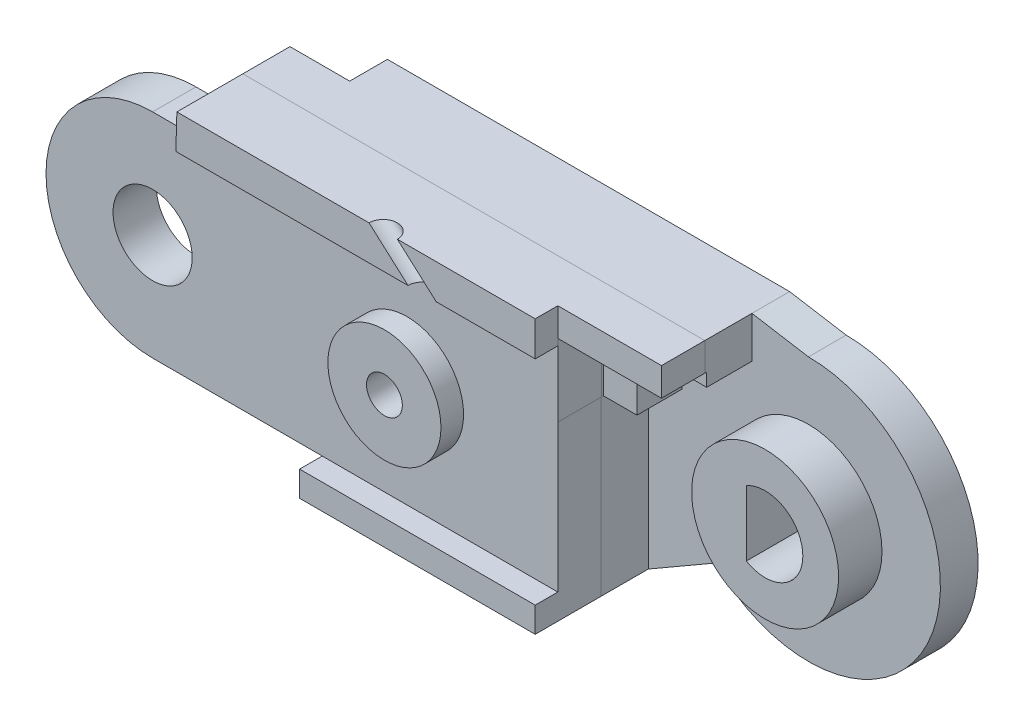
SolidWorks part; units mm, degrees
ref_plane "Front Plane" through (0, 0, 0) normal (0, 0, 1) x (1, 0, 0)
ref_plane "Top Plane" through (0, 0, 0) normal (0, 1, 0) x (1, 0, 0)
ref_plane "Right Plane" through (0, 0, 0) normal (1, 0, 0) x (0, 0, -1)
sketch "Sketch3" plane through (0, 0, 0) normal (0, 0, 1) x (1, 0, 0)
  line L7 (8, 0) -> (9, -2.5)
  line L11 (30, 7) -> (27, 7.5)
  line L13 (0, 7) -> (0, 7.5) construction
  line L14 (0, 7.5) -> (-22.3287, 7.5) construction
  line L15 (0, 5.3) -> (-14, 5.3) construction
  line L16 (0, 4) -> (-14, 4) construction
  line L17 (-14, 4) -> (-14, 5.3) construction
  line L18 (5.6569, 5.6569) -> (5.6569, 7.5)
  line L19 (5.6569, 7.5) -> (27, 7.5)
  line L20 (21.5, -7) -> (9, -7)
  line L21 (9, -7) -> (9, -2.5)
  line L23 (25.0503, -4.9497) -> (21.5, -7)
  arc A4 (8, 0) -> (5.6569, 5.6569) centre (0, 0) ccw
  arc A5 (25.0503, -4.9497) -> (30, 7) centre (30, 0) ccw
  circle A6 centre (0, 0) radius 7 construction
  circle A7 centre (0, 0) radius 3.9 construction
  circle A8 centre (0, 0) radius 5.3 construction
  circle A9 centre (0, 0) radius 4 construction
  dimension "D10" = 0.5
  dimension "D17" = 14
  dimension "D5" = 135
  dimension "D6" = 12.5
  dimension "D7" = 4.5
  dimension "D8" = 1
  dimension "D9" = 45
  dimension "D11" = 1.8431
  dimension "D12" = 30
  dimension "D14" = 3
extrude "Boss-Extrude1" add sketch "Sketch3" along normal blind 2 contours A5 L11 L19 L18 A4 L7 L21 L20 L23
sketch "Sketch20" plane through (0, 0, 0) normal (0, 0, 1) x (1, 0, 0)
  line L0 (0, 7) -> (0, 7.5) construction
  line L1 (0, 7.5) -> (-19.4737, 7.5) construction
  line L2 (0, 5.3) -> (-14, 5.3) construction
  line L3 (0, 4) -> (-14, 4) construction
  line L4 (-14, 4) -> (-14, 5.3) construction
  line L5 (0, 5.3) -> (17.4849, 5.3) construction
  line L6 (17.4849, 5.3) -> (17.4849, 4) construction
  line L7 (17.4849, 4) -> (0, 4) construction
  line L8 (-2.5, 7.5) -> (-2.5, 2.868) construction
  circle A0 centre (0, 0) radius 7 construction
  circle A1 centre (0, 0) radius 3.9 construction
  circle A3 centre (0, 0) radius 5.3 construction
  circle A4 centre (0, 0) radius 4 construction
  circle A5 centre (0, 0) radius 2 construction
  dimension "D1" = 0
  dimension "D2" = 2.5
ref_plane "Plane1" through (0, 0, 2) normal (0, 0, 1) x (1, 0, 0)
sketch "Sketch4" plane through (0, 0, 2) normal (0, 0, 1) x (1, 0, 0)
  line L4 (5.6569, 5.6569) -> (5.6569, 7.5)
  line L5 (5.6569, 5.6569) -> (5.6569, 7.5) construction
  line L6 (5.6569, 7.5) -> (21.5, 7.5)
  line L10 (8, 0) -> (9, -2.5)
  line L11 (9, -2.5) -> (9, -7)
  line L12 (9, -7) -> (21.5, -7)
  line L13 (21.5, -7) -> (21.5, 7.5)
  arc A0 (8, 0) -> (5.6569, 5.6569) centre (0, 0) ccw construction
  arc A3 (8, 0) -> (5.6569, 5.6569) centre (0, 0) ccw
sketch "Sketch22" plane through (0, 0, 2) normal (0, 0, 1) x (1, 0, 0)
  line L0 (5.6569, 5.6569) -> (2.4868, 5.6569)
  line L1 (5.6569, 7.5) -> (21.5, 7.5)
  line L2 (5.6569, 7.5) -> (2.4868, 7.5)
  line L3 (2.4868, 7.5) -> (2.4868, 5.6569)
  line L4 (21.5, 2.172) -> (21.5, 0)
  line L6 (8, 0) -> (9, -2.5)
  line L7 (9, -2.5) -> (9, -7)
  line L8 (9, -7) -> (21.5, -7)
  line L9 (21.5, -7) -> (21.5, 0)
  line L10 (21.5, 7.5) -> (27, 7.5)
  line L11 (27, 7.5) -> (27, 2.172)
  line L12 (27, 2.172) -> (21.5, 2.172)
  arc A0 (8, 0) -> (5.6569, 5.6569) centre (0, 0) ccw
extrude "Boss-Extrude6" add sketch "Sketch22" along normal blind 2.5
sketch "Sketch25" plane through (0, 0, 2) normal (0, 0, 1) x (1, 0, 0)
  line L0 (0, 5.3) -> (18.0981, 5.3) construction
  line L1 (0, 4) -> (18.0981, 4) construction
  line L2 (18.0981, 4) -> (18.0981, 5.3) construction
sketch "Sketch26" plane through (0, 0, 2) normal (0, 0, 1) x (1, 0, 0)
  line L1 (18.0981, 5.3) -> (2.5301, 5.3)
  line L2 (18.0981, 4) -> (2.5301, 4)
  line L3 (2.5301, 5.3) -> (2.5301, 4)
  line L4 (18.0981, 5.3) -> (27, 5.3)
  line L5 (27, 2.172) -> (27, 7.5) construction
  line L6 (27, 5.3) -> (27, 4)
  line L7 (27, 4) -> (18.0981, 4)
extrude "Cut-Extrude6" cut sketch "Sketch26" along normal blind 2.4
sketch "Sketch31" plane through (0, 0, 4.5) normal (0, 0, 1) x (1, 0, 0)
  line L0 (2.4327, 5.6569) -> (0, 5.6569)
  line L4 (9, -5.6569) -> (0, -5.6569)
  line L5 (2.4327, 5.6569) -> (2.4868, 7.5)
  line L6 (2.4868, 7.5) -> (21.5, 7.5)
  line L7 (21.5, -7) -> (21.5, 2.172) construction
  line L8 (27, 7.5) -> (2.4868, 7.5) construction
  line L11 (21.5, -7) -> (9, -7)
  line L12 (9, -7) -> (9, -5.6569)
  line L13 (9, -2.5) -> (9, -7) construction
  line L14 (21.5, 2.172) -> (21.5, -7)
  line L15 (21.5, 7.5) -> (27, 7.5)
  line L16 (27, 7.5) -> (27, 2.172)
  line L17 (27, 2.172) -> (21.5, 2.172)
  arc A0 (0, 5.6569) -> (0, -5.6569) centre (0, 0) ccw
  dimension "D1" = 5.6569
extrude "Boss-Extrude14" add sketch "Sketch31" along normal blind 2.3 separate body
sketch "Sketch32" plane through (0, 0, 6.8) normal (0, 0, 1) x (1, 0, 0)
  circle A0 centre (0, 0) radius 2.1
extrude "Cut-Extrude7" cut sketch "Sketch32" against normal blind 2.3
sketch "Sketch33" plane through (0, 0, 6.8) normal (0, 0, 1) x (1, 0, 0)
  line L0 (2.4868, 7.5) -> (21.5, 7.5)
  line L1 (27, 7.5) -> (2.4868, 7.5) construction
  line L6 (9, -5.6569) -> (21.5, -5.6569)
  line L7 (21.5, -7) -> (21.5, 2.172) construction
  line L8 (21.5, -5.6569) -> (21.5, -7)
  line L9 (21.5, -7) -> (9, -7)
  line L10 (9, -7) -> (9, -5.6569)
  line L12 (2.4868, 7.5) -> (2.4327, 5.6569)
  line L13 (2.4327, 5.6569) -> (21.5, 5.6569)
  line L14 (21.5, 5.6569) -> (21.5, 7.5)
extrude "Boss-Extrude15" add sketch "Sketch33" along normal blind 1.2
sketch "Sketch34" plane through (0, 0, 2) normal (0, 0, 1) x (1, 0, 0)
  line L0 (30, 5.3) -> (18.0981, 5.3) construction
  line L1 (30, 4) -> (18.0981, 4) construction
  circle A0 centre (30, 0) radius 2 construction
  circle A1 centre (30, 0) radius 5.3 construction
  circle A2 centre (30, 0) radius 4 construction
sketch "Sketch35" plane through (0, 0, 6.8) normal (0, 0, 1) x (1, 0, 0)
  line L0 (27, 2.172) -> (27, 6)
  line L1 (27, 2.172) -> (21.5204, 2.172)
  line L2 (27, 6) -> (21.5204, 6)
  line L3 (21.5204, 2.172) -> (21.5204, 6)
  line L4 (27, 2.172) -> (27, 7.5) construction
  line L5 (27, 7.5) -> (21.5, 7.5) construction
  dimension "D1" = 1.5
extrude "Cut-Extrude8" cut sketch "Sketch35" against normal blind 2.4
sketch "Sketch36" plane through (0, 0, 4.4) normal (0, 0, 1) x (1, 0, 0)
  line L0 (27, 2.172) -> (27, 4)
  line L1 (27, 2.172) -> (23.3, 2.172)
  line L2 (27, 4) -> (23.3, 4)
  line L3 (23.3, 2.172) -> (23.3, 4)
  line L4 (21.5, -7) -> (21.5, 7.5) construction
  dimension "D1" = 1.8
extrude "Cut-Extrude9" cut sketch "Sketch36" against normal blind 2.4
sketch "Sketch37" plane through (0, 0, 2) normal (0, 0, 1) x (1, 0, 0)
  circle A0 centre (30, 0) radius 3.9
extrude "Boss-Extrude16" add sketch "Sketch37" along normal blind 2.3
sketch "Sketch39" plane through (0, 0, 4.3) normal (0, 0, 1) x (1, 0, 0)
  line L0 (29, 1.7321) -> (29, -1.7321)
  arc A0 (29, -1.7321) -> (29, 1.7321) centre (30, 0) ccw
  dimension "D2" = 4
  dimension "D1" = 1
extrude "Cut-Extrude10" cut sketch "Sketch39" against normal through all
sketch "Sketch43" plane through (0, 0, 6.8) normal (0, 0, 1) x (1, 0, 0)
  line L0 (21.5, -7) -> (21.5, 7.5) construction
  line L1 (21.5, -5.6569) -> (9, -5.6569) construction
  circle A0 centre (13.5, 0) radius 3
  dimension "D1" = 8
  dimension "D2" = 5.6569
extrude "Boss-Extrude17" add sketch "Sketch43" along normal blind 1.2
sketch "Sketch44" plane through (0, 0, 8) normal (0, 0, 1) x (1, 0, 0)
  circle A0 centre (13.5, 0) radius 0.95
extrude "Cut-Extrude11" cut sketch "Sketch44" against normal through all
sketch "Sketch45" plane through (0, 0, 0) normal (0, 0, -1) x (-1, 0, 0)
  circle A0 centre (-13.5, 0) radius 2
extrude "Cut-Extrude12" cut sketch "Sketch45" against normal blind 3.2
ref_plane "Plane17" through (0, 0, 8) normal (0, 0, 1) x (1, 0, 0)
sketch "Sketch46" plane through (0, 0, 8) normal (0, 0, 1) x (1, 0, 0)
  line L0 (15.5, 5.6569) -> (27.1062, -4.6961) construction
  line L1 (2.4327, 5.6569) -> (21.5, 5.6569) construction
  line L2 (21.5, 5.6569) -> (21.5, 7.5) construction
  dimension "D1" = 6
sketch "Sketch47" plane through (0, 5.6569, 0) normal (0, -1, 0) x (1, 0, 0)
  circle A0 centre (15.5, 8) radius 0.75
extrude "Cut-Extrude13" cut sketch "Sketch47" along direction (0.7462, -0.6657, 0) on the side against the normal blind 5.2
